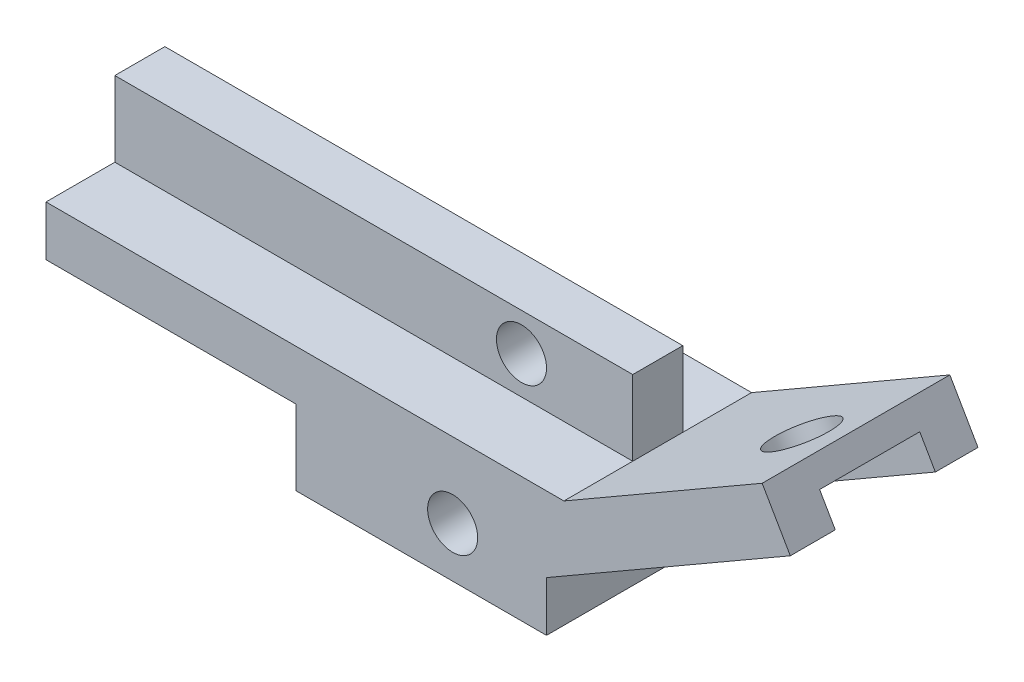
SolidWorks part; units mm, degrees
ref_plane "정면" through (0, 0, 0) normal (0, 0, 1) x (1, 0, 0)
ref_plane "윗면" through (0, 0, 0) normal (0, 1, 0) x (1, 0, 0)
ref_plane "우측면" through (0, 0, 0) normal (1, 0, 0) x (0, 0, -1)
sketch "스케치1" plane through (0, 0, 0) normal (0, 0, 1) x (1, 0, 0)
  line L0 (0, 0) -> (40, 0)
  line L1 (40, 0) -> (40, -12)
  line L2 (40, -12) -> (80, -12)
  line L3 (80, -12) -> (80, -4)
  line L4 (80, -4) -> (118.9711, 18.5)
  line L5 (118.9711, 18.5) -> (114.4711, 26.2942)
  line L6 (114.4711, 26.2942) -> (82.7846, 8)
  line L7 (82.7846, 8) -> (0, 8)
  line L8 (0, 8) -> (0, 0)
  line L9 (82.7846, 8) -> (82.7846, 20)
  line L10 (82.7846, 20) -> (0, 20)
  line L11 (0, 20) -> (0, 8)
  line L12 (65, -4) -> (65, 35.0079) construction
  circle A1 centre (65, -4) radius 4
  circle A2 centre (65, -4) radius 4
  circle A3 centre (65, 14) radius 4
  dimension "D10" = 8
  dimension "D11" = 6
  dimension "D13" = 8
  dimension "D1" = 40
  dimension "D2" = 12
  dimension "D3" = 40
  dimension "D4" = 8
  dimension "D5" = 45
  dimension "D6" = 9
  dimension "D7" = 60
  dimension "D8" = 8
  dimension "D9" = 20
  dimension "D12" = 8
  dimension "D14" = 15
extrude "보스-돌출4" add sketch "스케치1" along normal mid plane 30 contours A1 L7 L8 L0 L1 L2 L3 L4 L5 L6 region at (61.1305, 3.0023, 0)
extrude "보스-돌출5" add sketch "스케치1<15>" along normal mid plane 8 contours L7 L12 A3 L10 L11 | L12 L7 L9 L10 A3 region at (31.4745, 14, 0) region at (74.8527, 14, 0)
sketch "스케치1<15>" plane through (0, 0, 0) normal (0, 0, 1) x (1, 0, 0) same geometry as "스케치1"
sketch "스케치15" plane through (17.2321, -29.8468, 0) normal (-0.5, 0.866, 0) x (0.866, 0.5, 0)
  line L0 (67.282, 0) -> (112.282, 0) construction
  line L1 (112.282, -15) -> (112.282, 15) construction
  circle A0 centre (102.282, 0) radius 5
  dimension "D1" = 10
  dimension "D2" = 10
extrude "컷-돌출9" cut sketch "스케치15" against normal through all contours A0 region at (105.8109, 21.2942, 0)
sketch "스케치16" plane through (97.2391, 56.141, 0) normal (0.866, 0.5, 0) x (0, 0, -1)
  line L0 (8.1882, -43.4641) -> (8.1882, -38.4641)
  line L1 (-15, -43.4641) -> (15, -43.4641) construction
  line L2 (8.1882, -38.4641) -> (-7.8118, -38.4641)
  line L3 (-7.8118, -38.4641) -> (-7.8118, -43.4641)
  line L4 (-15, -43.4641) -> (15, -43.4641) construction
  line L5 (-7.8118, -43.4641) -> (8.1882, -43.4641)
  line L6 (-15, -34.4641) -> (15, -34.4641) construction
  line M8 (-15, -43.4641) -> (15, -43.4641)
  dimension "D1" = 16
  dimension "D2" = 4
extrude "컷-돌출10" cut sketch "스케치16" against normal blind 30 contours L2 L3 L0 M8 region at (117.7211, 20.6651, -0.1882)
